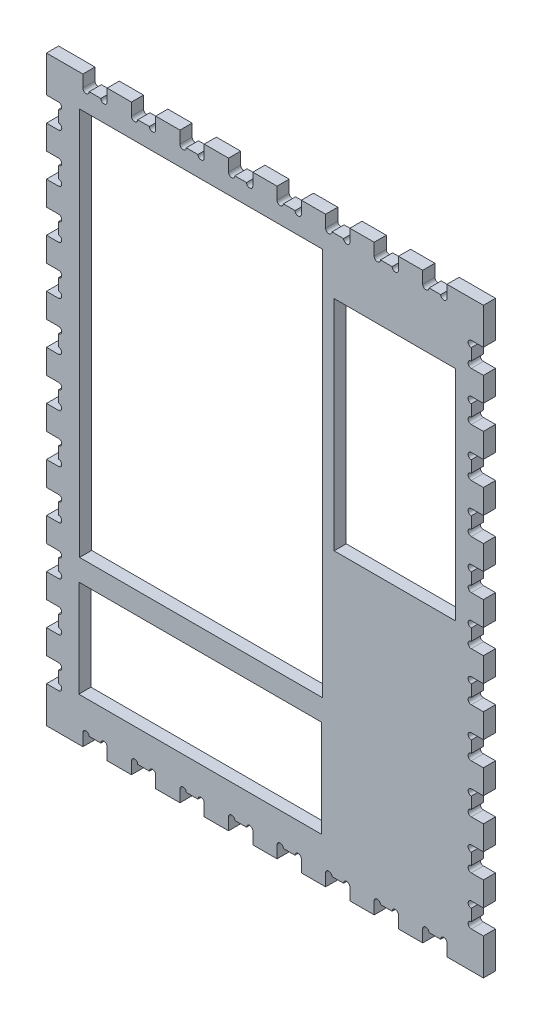
SolidWorks part; units mm, degrees
ref_plane "Front Plane" through (0, 0, 0) normal (0, 0, 1) x (1, 0, 0)
ref_plane "Top Plane" through (0, 0, 0) normal (0, 1, 0) x (1, 0, 0)
ref_plane "Right Plane" through (0, 0, 0) normal (1, 0, 0) x (0, 0, -1)
sketch "Sketch1" plane through (0, 0, 0) normal (0, 0, 1) x (1, 0, 0)
  line L1 (228.6, -304.8) -> (-228.6, -304.8)
  line L2 (228.6, -304.8) -> (228.6, 304.8)
  line L3 (228.6, 304.8) -> (-228.6, 304.8)
  line L4 (-228.6, -304.8) -> (-228.6, 304.8)
  line L5 (228.6, -304.8) -> (-228.6, 304.8) construction
  line L6 (228.6, 304.8) -> (-228.6, -304.8) construction
  line L9 (-203.2, 304.8) -> (-228.6, 304.8) construction
  point P0 (0, 0)
  dimension "D1" = 457.2
  dimension "D2" = 609.6
extrude "Boss-Extrude1" add sketch "Sketch1" along normal blind 12.7
sketch "Sketch2" plane through (0, 0, 12.7) normal (0, 0, 1) x (1, 0, 0)
  line L0 (228.6, 304.8) -> (-228.6, 304.8) construction
  line L1 (-190.5, 292.1) -> (-228.6, 292.1) construction
  line L2 (-190.5, 304.8) -> (-165.1, 304.8)
  line L3 (-190.5, 304.8) -> (-190.5, 292.1)
  line L4 (-190.5, 292.1) -> (-165.1, 292.1)
  line L5 (-165.1, 304.8) -> (-165.1, 292.1)
  line L6 (-228.6, 304.8) -> (-228.6, -304.8) construction
  circle A0 centre (-187.198, 292.1) radius 3.302
  circle A1 centre (-168.402, 292.1) radius 3.302
  line M10 (228.6, 304.8) -> (-228.6, 304.8)
  dimension "D4" = 6.604
  dimension "D5" = 6.604
  dimension "D1" = 25.4
  dimension "D2" = 12.7
  dimension "D3" = 38.1
extrude "Cut-Extrude1" cut sketch "Sketch2" against normal through all contours A1 L5 L3 A0 L4 M10 | L4 A0 | L4 A0 | L4 A1 | L4 A1 region at (-177.8, 299.0379, 12.7) region at (-187.198, 293.5014, 12.7) region at (-187.198, 290.6986, 12.7) region at (-168.402, 290.6986, 12.7) region at (-168.402, 293.5014, 12.7)
pattern_linear "LPattern1" count 8 spacing 50.8 along (1, 0, 0) of "Cut-Extrude1"
sketch "Sketch3" plane through (0, 0, 12.7) normal (0, 0, 1) x (1, 0, 0)
  line L0 (-228.6, 304.8) -> (-228.6, -304.8) construction
  line L1 (-228.6, 266.7) -> (-215.9, 266.7)
  line L2 (-228.6, 266.7) -> (-228.6, 241.3)
  line L3 (-228.6, 241.3) -> (-215.9, 241.3)
  line L4 (-215.9, 266.7) -> (-215.9, 241.3)
  line L5 (-215.9, 266.7) -> (-215.9, 304.8) construction
  line L7 (-190.5, 304.8) -> (-228.6, 304.8) construction
  circle A0 centre (-215.9, 263.398) radius 3.302
  circle A1 centre (-215.9, 244.602) radius 3.302
  dimension "D3" = 6.604
  dimension "D4" = 6.604
  dimension "D1" = 25.4
  dimension "D2" = 12.7
  dimension "D5" = 38.1
extrude "Cut-Extrude2" cut sketch "Sketch3" against normal through all contours A1 L4 A0 L1 L2 L3 | L4 A0 | L4 A1 | L4 A1 | L4 A0 region at (-222.8379, 254, 12.7) region at (-214.4986, 263.398, 12.7) region at (-217.3014, 263.398, 12.7) region at (-217.3014, 244.602, 12.7) region at (-214.4986, 244.602, 12.7)
pattern_linear "LPattern2" count 11 spacing 50.8 along (0, -1, 0) of "Cut-Extrude2"
ref_plane "Plane1" through (0, 0, 0) normal (1, 0, 0) x (0, 0, -1)
ref_plane "Plane2" through (0, 0, 0) normal (0, 1, 0) x (1, 0, 0)
mirror "Mirror1" about plane through (0, 0, 0) normal (1, 0, 0) of "LPattern2"
mirror "Mirror2" about plane through (0, 0, 0) normal (0, 1, 0) of "LPattern1"
sketch "Sketch4" plane through (0, 0, 0) normal (0, 0, -1) x (-1, 0, 0)
  line L1 (193.9718, -134.9698) -> (-60.0282, -134.9698)
  line L2 (193.9718, -134.9698) -> (193.9718, 271.4302)
  line L3 (193.9718, 271.4302) -> (-60.0282, 271.4302)
  line L4 (-60.0282, -134.9698) -> (-60.0282, 271.4302)
  line L5 (-72.3846, 4.1995) -> (-199.3846, 4.1995)
  line L6 (-72.3846, 4.1995) -> (-72.3846, 232.7995)
  line L7 (-72.3846, 232.7995) -> (-199.3846, 232.7995)
  line L8 (-199.3846, 4.1995) -> (-199.3846, 232.7995)
  line L9 (194.792, -259.2749) -> (-59.208, -259.2749)
  line L10 (194.792, -259.2749) -> (194.792, -157.6749)
  line L11 (194.792, -157.6749) -> (-59.208, -157.6749)
  line L12 (-59.208, -259.2749) -> (-59.208, -157.6749)
  dimension "D1" = 406.4
  dimension "D2" = 254
  dimension "D3" = 101.6
  dimension "D4" = 127
  dimension "D5" = 228.6
extrude "Cut-Extrude3" cut sketch "Sketch4" against normal through all
